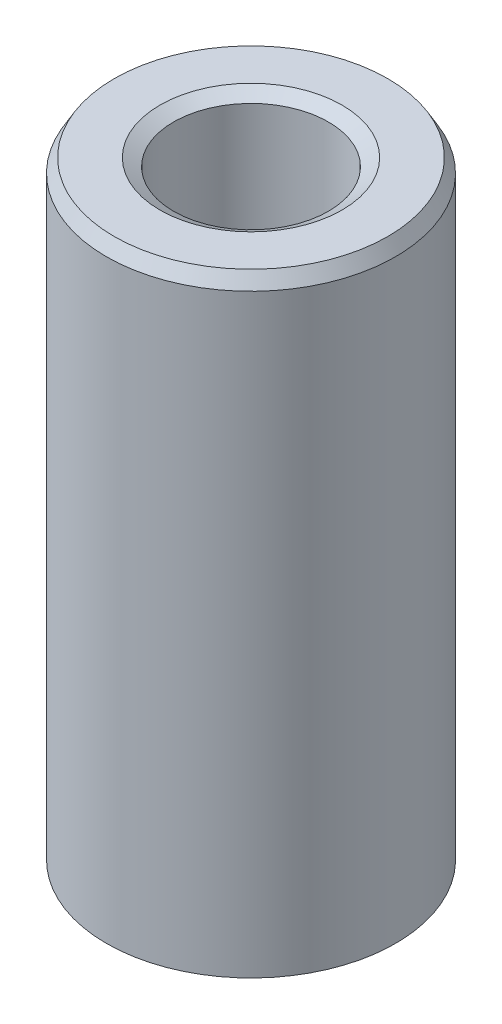
SolidWorks part; units mm, degrees
ref_plane "Front Plane" through (0, 0, 0) normal (0, 0, 1) x (1, 0, 0)
ref_plane "Top Plane" through (0, 0, 0) normal (0, 1, 0) x (1, 0, 0)
ref_plane "Right Plane" through (0, 0, 0) normal (1, 0, 0) x (0, 0, -1)
sketch "Sketch1" plane through (0, 0, 0) normal (0, 1, 0) x (1, 0, 0)
  circle A0 centre (0, 0) radius 22.5
  dimension "SLEEVE_OD" = 45
extrude "Boss-Extrude1" add sketch "Sketch1" along normal blind 95.8579
sketch "Sketch2" plane through (0, 0, 0) normal (0, 1, 0) x (1, 0, 0)
  circle A0 centre (0, 0) radius 12.0464
  dimension "BORE_D" = 24.0928
extrude "Cut-Extrude1" cut sketch "Sketch2" along normal through all
chamfer "Chamfer1" distance 2.1116 angle 30 4 edges at (0, 95.8579, 12.0464) (0, 0, 12.0464) (0, 0, 22.5) (0, 95.8579, 22.5) first distance on face at (0, 95.8579, 12.0464) first distance on face at (0, 0, 12.0464) first distance on face at (0, 95.8579, 22.5)
